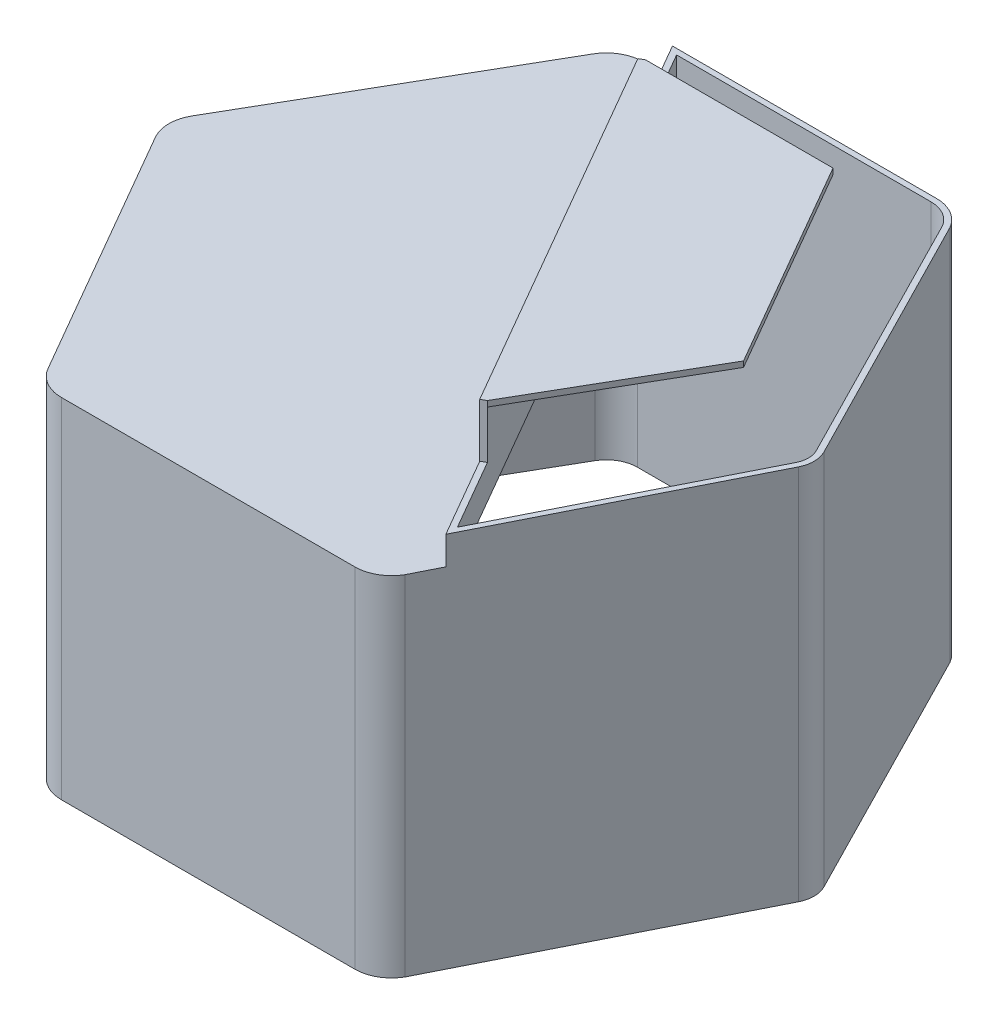
SolidWorks part; units mm, degrees
material "PUR"
ref_plane "Alzado" through (0, 0, 0) normal (0, 0, 1) x (1, 0, 0)
ref_plane "Planta" through (0, 0, 0) normal (0, 1, 0) x (1, 0, 0)
ref_plane "Vista lateral" through (0, 0, 0) normal (1, 0, 0) x (0, 0, -1)
sketch "Croquis1" plane through (0, 0, 0) normal (0, 1, 0) x (1, 0, 0)
  line L0 (65.5921, 95.5805) -> (112.1694, 4.3292)
  line L2 (65.5921, -97.4195) -> (112.1973, -4.7085)
  line L4 (-60.8476, 95.5805) -> (-112.8091, 5.5805)
  line L5 (-112.8091, -7.4195) -> (-60.8476, -97.4195)
  line L6 (-49.5893, -103.9195) -> (54.3338, -103.9195)
  line L7 (117.5118, -7.492) -> (117.5536, -7.4195)
  line L8 (54.3338, 102.0805) -> (-49.5893, 102.0805)
  line L9 (63.8352, 94.6233) -> (110.3881, 3.42)
  line L10 (63.8322, -96.4674) -> (110.4103, -3.8102)
  line L11 (-49.5893, -101.9195) -> (54.3338, -101.9195)
  line L12 (-111.0771, -6.4195) -> (-59.1156, -96.4195)
  line L13 (-59.1156, 94.5805) -> (-111.0771, 4.5805)
  line L14 (54.3338, 100.0805) -> (-49.5893, 100.0805)
  line L15 (115.7797, -6.492) -> (115.8216, -6.4195)
  line L18 (95.3063, -0.9195) -> (95.008, -0.9195) construction
  arc A0 (112.1973, -4.7085) -> (112.1694, 4.3292) centre (103.2626, -0.2171) ccw
  arc A1 (-49.5893, 102.0805) -> (-60.8476, 95.5805) centre (-49.5893, 89.0805) ccw
  arc A2 (-112.8091, 5.5805) -> (-112.8091, -7.4195) centre (-101.5508, -0.9195) ccw
  arc A3 (-60.8476, -97.4195) -> (-49.5893, -103.9195) centre (-49.5893, -90.9195) ccw
  arc A4 (54.3338, -103.9195) -> (65.5921, -97.4195) centre (54.3338, -90.9195) ccw
  arc A5 (65.5921, 95.5805) -> (54.3338, 102.0805) centre (54.3338, 89.0805) ccw
  arc A7 (54.3338, -101.9195) -> (63.8322, -96.4674) centre (54.3338, -90.9195) ccw
  arc A8 (-59.1156, -96.4195) -> (-49.5893, -101.9195) centre (-49.5893, -90.9195) ccw
  arc A9 (-111.0771, 4.5805) -> (-111.0771, -6.4195) centre (-101.5508, -0.9195) ccw
  arc A10 (-49.5893, 100.0805) -> (-59.1156, 94.5805) centre (-49.5893, 89.0805) ccw
  arc A11 (63.8352, 94.6233) -> (54.3338, 100.0805) centre (54.3338, 89.0805) ccw
  arc A12 (111.2626, -0.1925) -> (110.3881, 3.42) centre (103.2626, -0.2171) ccw
  arc A13 (110.4103, -3.8102) -> (110.3881, 3.42) centre (103.2626, -0.2171) ccw construction
  arc A14 (110.4103, -3.8102) -> (111.2626, -0.1925) centre (103.2626, -0.2171) ccw
  point P4 (0, 0)
  point P5 (111.2618, -0.1939)
  point P7 (111.2626, -0.1928)
  dimension "D1" = 10
  dimension "D2" = 2
extrude "Saliente-Extruir1" add sketch "Croquis1" along normal blind 123.4 contours A11 L9 A0 L0 A5 L8 A1 L4 A2 L5 A3 L6 A4 L2 L10 A7 L11 A8 L12 A9 L13 A10 L14 region at (88.6072, 0, -49.8152)
sketch "Croquis2" plane through (0, 123.4, 0) normal (0, 1, 0) x (1, 0, 0)
  line L0 (-78.1819, 169.6043) -> (130.4043, -191.6776)
  line L2 (71.6543, -90.9195) -> (-40.929, 104.0805) construction
  line L3 (58.6639, -68.4195) -> (-27.9386, 81.5805) construction
  line L6 (112.1694, 4.3292) -> (65.5921, 95.5805)
  line L7 (54.3338, 102.0805) -> (-49.5893, 102.0805)
  line L8 (-60.8476, 95.5805) -> (-112.8091, 5.5805)
  line L9 (-112.8091, -7.4195) -> (-60.8476, -97.4195)
  line L10 (-49.5893, -103.9195) -> (54.3338, -103.9195)
  line L11 (65.5921, -97.4195) -> (112.1973, -4.7085)
  line L12 (112.1694, 4.3292) -> (65.5921, 95.5805)
  line L13 (54.3338, 102.0805) -> (-49.5893, 102.0805)
  line L14 (-60.8476, 95.5805) -> (-112.8091, 5.5805)
  line L15 (-112.8091, -7.4195) -> (-60.8476, -97.4195)
  line L16 (-49.5893, -103.9195) -> (54.3338, -103.9195)
  line L17 (65.5921, -97.4195) -> (112.1973, -4.7085)
  arc A6 (65.5921, 95.5805) -> (54.3338, 102.0805) centre (54.3338, 89.0805) ccw
  arc A7 (-49.5893, 102.0805) -> (-60.8476, 95.5805) centre (-49.5893, 89.0805) ccw
  arc A8 (-112.8091, 5.5805) -> (-112.8091, -7.4195) centre (-101.5508, -0.9195) ccw
  arc A9 (-60.8476, -97.4195) -> (-49.5893, -103.9195) centre (-49.5893, -90.9195) ccw
  arc A10 (54.3338, -103.9195) -> (65.5921, -97.4195) centre (54.3338, -90.9195) ccw
  arc A11 (112.1973, -4.7085) -> (112.1694, 4.3292) centre (103.2626, -0.2171) ccw
  arc A12 (65.5921, 95.5805) -> (54.3338, 102.0805) centre (54.3338, 89.0805) ccw
  arc A13 (-49.5893, 102.0805) -> (-60.8476, 95.5805) centre (-49.5893, 89.0805) ccw
  arc A14 (-112.8091, 5.5805) -> (-112.8091, -7.4195) centre (-101.5508, -0.9195) ccw
  arc A15 (-60.8476, -97.4195) -> (-49.5893, -103.9195) centre (-49.5893, -90.9195) ccw
  arc A16 (54.3338, -103.9195) -> (65.5921, -97.4195) centre (54.3338, -90.9195) ccw
  arc A17 (112.1973, -4.7085) -> (112.1694, 4.3292) centre (103.2626, -0.2171) ccw
  point P12 (72.641, 98.7357)
  point P18 (65.5921, 90.5862)
  point P25 (-78.3551, 169.5043)
  line M20 (54.3338, -101.9195) -> (-49.5893, -101.9195)
  arc M21 (-49.5893, -101.9195) -> (-59.1156, -96.4195) centre (-49.5893, -90.9195) cw
  line M22 (-59.1156, -96.4195) -> (-111.0771, -6.4195)
  arc M23 (-111.0771, -6.4195) -> (-111.0771, 4.5805) centre (-101.5508, -0.9195) cw
  line M24 (-111.0771, 4.5805) -> (-59.1156, 94.5805)
  arc M25 (-59.1156, 94.5805) -> (-49.5893, 100.0805) centre (-49.5893, 89.0805) cw
  line M26 (-49.5893, 100.0805) -> (54.3338, 100.0805)
  arc M27 (54.3338, 100.0805) -> (63.8352, 94.6233) centre (54.3338, 89.0805) cw
  line M28 (63.8352, 94.6233) -> (110.3881, 3.42)
  dimension "D2" = 0.5
  dimension "D1" = 0
extrude "Saliente-Extruir2" add sketch "Croquis2" against normal blind 2 contours L0 M28 M27 M26 M25 M24 M23 M22 M21 M20 region at (-29.7789, 123.4, 19.463)
sketch "Croquis3" plane through (0, 123.4, 0) normal (0, 1, 0) x (1, 0, 0)
  line L0 (-38.0423, 100.0805) -> (69.2325, -85.7248) construction
  line L1 (-38.0423, 100.0805) -> (69.2325, -85.7248)
  line L2 (-36.3102, 101.0805) -> (70.9645, -84.7248)
  line L3 (-38.0423, 100.0805) -> (-36.3102, 101.0805)
  line L4 (69.2325, -85.7248) -> (70.9645, -84.7248)
  dimension "D1" = 2
extrude "Saliente-Extruir4" add sketch "Croquis3" along normal blind 10 and the other way blind 2
sketch "Croquis6" plane through (0, 123.4, 0) normal (0, 1, 0) x (1, 0, 0)
  line L3 (70.3073, -83.5865) -> (110.4103, -3.8102) construction
  line L21 (63.8352, 94.6233) -> (110.3881, 3.42) construction
  line L22 (54.3338, 100.0805) -> (-35.7329, 100.0805) construction
  line L23 (69.2325, -85.7248) -> (110.4103, -3.8102)
  line L25 (112.1694, 4.3292) -> (65.5921, 95.5805)
  line L26 (54.3338, 102.0805) -> (-49.5893, 102.0805)
  line L27 (-60.8476, 95.5805) -> (-112.8091, 5.5805)
  line L28 (-112.8091, -7.4195) -> (-60.8476, -97.4195)
  line L29 (-49.5893, -103.9195) -> (54.3338, -103.9195)
  line L30 (65.5921, -97.4195) -> (112.1973, -4.7085)
  line L31 (112.1694, 4.3292) -> (65.5921, 95.5805)
  line L32 (54.3338, 102.0805) -> (-49.5893, 102.0805)
  line L33 (-60.8476, 95.5805) -> (-112.8091, 5.5805)
  line L34 (-112.8091, -7.4195) -> (-60.8476, -97.4195)
  line L35 (-49.5893, -103.9195) -> (54.3338, -103.9195)
  line L36 (65.5921, -97.4195) -> (112.1973, -4.7085)
  line L37 (63.8352, 94.6233) -> (110.3881, 3.42)
  line L38 (54.3338, 100.0805) -> (-38.0423, 100.0805)
  line L39 (69.2325, -85.7248) -> (70.4291, -87.7974)
  line L40 (-38.0423, 100.0805) -> (-39.197, 102.0805)
  line L41 (-38.0423, 100.0805) -> (69.2325, -85.7248) construction
  line L42 (-38.0423, 100.0805) -> (69.2325, -85.7248) construction
  line L43 (54.3338, 102.0805) -> (-49.5893, 102.0805) construction
  arc A0 (110.4103, -3.8102) -> (110.3881, 3.42) centre (103.2626, -0.2171) ccw construction
  arc A1 (110.4103, -3.8102) -> (110.3881, 3.42) centre (103.2626, -0.2171) ccw construction
  arc A10 (63.8352, 94.6233) -> (54.3338, 100.0805) centre (54.3338, 89.0805) ccw construction
  arc A15 (110.4103, -3.8102) -> (110.3881, 3.42) centre (103.2626, -0.2171) ccw
  arc A16 (110.4103, -3.8102) -> (110.3881, 3.42) centre (103.2626, -0.2171) ccw
  arc A17 (63.8352, 94.6233) -> (54.3338, 100.0805) centre (54.3338, 89.0805) ccw
  arc A18 (65.5921, 95.5805) -> (54.3338, 102.0805) centre (54.3338, 89.0805) ccw
  arc A19 (-49.5893, 102.0805) -> (-60.8476, 95.5805) centre (-49.5893, 89.0805) ccw
  arc A20 (-112.8091, 5.5805) -> (-112.8091, -7.4195) centre (-101.5508, -0.9195) ccw
  arc A21 (-60.8476, -97.4195) -> (-49.5893, -103.9195) centre (-49.5893, -90.9195) ccw
  arc A22 (54.3338, -103.9195) -> (65.5921, -97.4195) centre (54.3338, -90.9195) ccw
  arc A23 (112.1973, -4.7085) -> (112.1694, 4.3292) centre (103.2626, -0.2171) ccw
  arc A24 (65.5921, 95.5805) -> (54.3338, 102.0805) centre (54.3338, 89.0805) ccw
  arc A25 (-49.5893, 102.0805) -> (-60.8476, 95.5805) centre (-49.5893, 89.0805) ccw
  arc A26 (-112.8091, 5.5805) -> (-112.8091, -7.4195) centre (-101.5508, -0.9195) ccw
  arc A27 (-60.8476, -97.4195) -> (-49.5893, -103.9195) centre (-49.5893, -90.9195) ccw
  arc A28 (54.3338, -103.9195) -> (65.5921, -97.4195) centre (54.3338, -90.9195) ccw
  arc A29 (112.1973, -4.7085) -> (112.1694, 4.3292) centre (103.2626, -0.2171) ccw
  point P2 (-38.0423, 100.0805)
  point P37 (-39.4192, 102.0805)
  point P40 (69.2233, -85.7089)
  line M2 (110.4103, -3.8102) -> (70.3073, -83.5865)
  line M4 (-35.7329, 100.0805) -> (54.3338, 100.0805)
  arc M5 (54.3338, 100.0805) -> (63.8352, 94.6233) centre (54.3338, 89.0805) cw
  line M6 (63.8352, 94.6233) -> (110.3881, 3.42)
  arc M7 (110.3881, 3.42) -> (110.4103, -3.8102) centre (103.2626, -0.2171) cw
  line M11 (112.1694, 4.3292) -> (65.5921, 95.5805)
  arc M12 (65.5921, 95.5805) -> (54.3338, 102.0805) centre (54.3338, 89.0805) ccw
  line M13 (54.3338, 102.0805) -> (-49.5893, 102.0805)
  arc M22 (112.1973, -4.7085) -> (112.1694, 4.3292) centre (103.2626, -0.2171) ccw
  line M37 (-38.0423, 100.0805) -> (-36.3102, 101.0805)
  line M38 (-36.3102, 101.0805) -> (-35.7329, 100.0805)
  line M39 (70.3073, -83.5865) -> (70.9645, -84.7248)
  line M40 (70.9645, -84.7248) -> (69.2325, -85.7248)
  arc M42 (110.3881, 3.42) -> (110.4103, -3.8102) centre (103.2626, -0.2171) cw
  dimension "D1" = 0
sketch "Croquis7" plane through (0, 133.4, 0) normal (0, 1, 0) x (1, 0, 0)
  line L4 (-38.0423, 100.0805) -> (69.2325, -85.7248)
  line L5 (-36.3102, 101.0805) -> (-38.0423, 100.0805)
  line L6 (-36.3102, 101.0805) -> (-38.0423, 100.0805)
  line L7 (69.2325, -85.7248) -> (70.9645, -84.7248)
  line L8 (-38.0423, 100.0805) -> (69.2325, -85.7248)
  line L12 (69.2325, -85.7248) -> (70.9645, -84.7248)
  line L13 (70.9645, -84.7248) -> (-36.3102, 101.0805)
  line L14 (70.9645, -84.7248) -> (-36.3102, 101.0805)
  dimension "D1" = 0
extrude "Saliente-Extruir6" add sketch "Croquis7" against normal blind 2
extrude "Saliente-Extruir7" add sketch "Croquis6" along normal up to surface (10 mm away) contours L40 L39 L36 M37 M38 M4 M5 M6 M7 M42 M2 M39 M40 M22 M11 M12 M13 region at (70.2202, 123.4, 85.4357) up to face at (16.4611, 133.4, -7.6778)
sketch "Croquis10" plane through (0, 133.4, 0) normal (0, 1, 0) x (1, 0, 0)
  line L6 (-40.929, 74.0805) -> (45.6735, 74.0805) construction
  line L7 (45.6735, 74.0805) -> (88.393, 0.0882) construction
  line L9 (80.323, -15.9048) -> (77.823, -20.2349) construction
  line L10 (70.3073, -83.5865) -> (-35.7329, 100.0805) construction
  line L12 (-20.7218, 74.0805) -> (55.7771, -58.4195)
  line L13 (55.7771, -58.4195) -> (88.9748, -0.9195)
  line L14 (88.9748, -0.9195) -> (45.6735, 74.0805)
  line L15 (45.6735, 74.0805) -> (-20.7218, 74.0805)
extrude "Saliente-Extruir9" add sketch "Croquis10" along normal blind 19 separate body
sketch "Croquis14" plane through (0, 133.4, 0) normal (0, -1, 0) x (1, 0, 0)
  line L4 (-20.7218, -74.0805) -> (45.6735, -74.0805)
  line L5 (45.6735, -74.0805) -> (88.9748, 0.9195)
  line L6 (88.9748, 0.9195) -> (55.7771, 58.4195)
  line L7 (55.7771, 58.4195) -> (-20.7218, -74.0805)
  line L8 (-20.7218, -74.0805) -> (45.6735, -74.0805)
  line L9 (45.6735, -74.0805) -> (88.9748, 0.9195)
  line L10 (88.9748, 0.9195) -> (55.7771, 58.4195)
  line L11 (55.7771, 58.4195) -> (-20.7218, -74.0805)
  dimension "D1" = 0
extrude "Cortar-Extruir2" cut sketch "Croquis14" against normal blind 17
sketch "Croquis16" plane through (0, 152.4, 0) normal (0, 1, 0) x (1, 0, 0)
  line L0 (-20.7218, 74.0805) -> (55.7771, -58.4195) construction
  line L1 (-20.7218, 74.0805) -> (55.7771, -58.4195)
  line L3 (-20.7218, 74.0805) -> (-22.4538, 73.0805)
  line L4 (-39.197, 102.0805) -> (70.4291, -87.7974) construction
  line L5 (55.7771, -58.4195) -> (54.0451, -59.4195)
  line L12 (65.5921, -97.4195) -> (70.4291, -87.7974)
  line L13 (70.4291, -87.7974) -> (-39.197, 102.0805)
  line L14 (-39.197, 102.0805) -> (-49.5893, 102.0805)
  line L15 (-60.8476, 95.5805) -> (-112.8091, 5.5805)
  line L16 (-112.8091, -7.4195) -> (-60.8476, -97.4195)
  line L17 (-49.5893, -103.9195) -> (54.3338, -103.9195)
  line L19 (54.0451, -59.4195) -> (-22.4538, 73.0805)
  arc A4 (-49.5893, 102.0805) -> (-60.8476, 95.5805) centre (-49.5893, 89.0805) ccw
  arc A5 (-112.8091, 5.5805) -> (-112.8091, -7.4195) centre (-101.5508, -0.9195) ccw
  arc A6 (-60.8476, -97.4195) -> (-49.5893, -103.9195) centre (-49.5893, -90.9195) ccw
  arc A7 (54.3338, -103.9195) -> (65.5921, -97.4195) centre (54.3338, -90.9195) ccw
  dimension "D1" = 0
extrude "Saliente-Extruir11" add sketch "Croquis16" against normal up to surface (19 mm away) up to face at (62.5222, 133.4, -35.3462)
